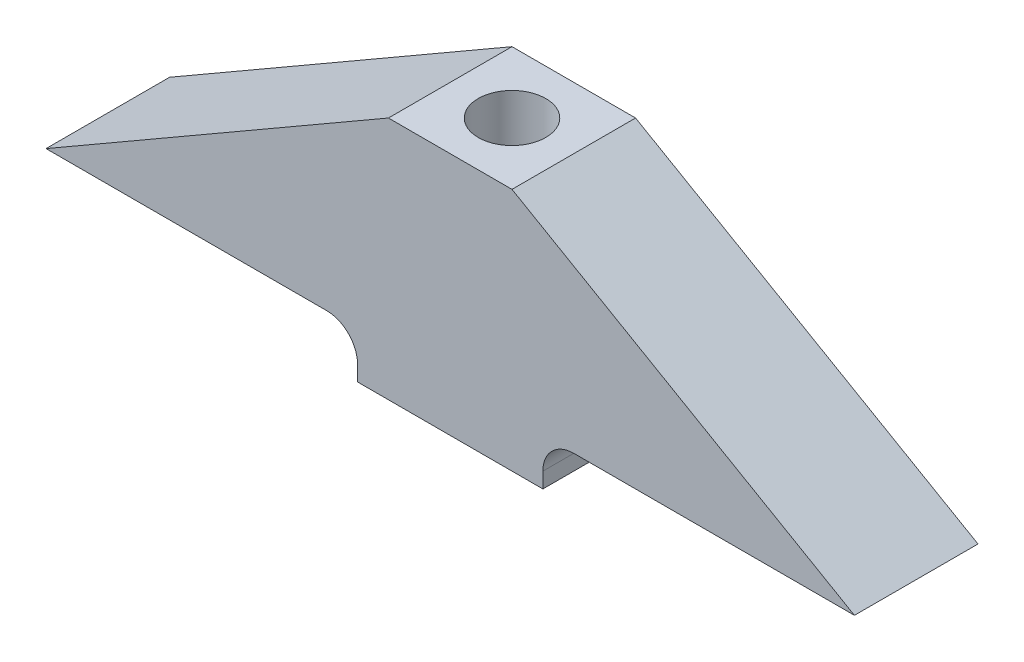
SolidWorks part; units mm, degrees
material "6061-T6 (SS)"
ref_plane "Front Plane" through (0, 0, 0) normal (0, 0, 1) x (1, 0, 0)
ref_plane "Top Plane" through (0, 0, 0) normal (0, 1, 0) x (1, 0, 0)
ref_plane "Right Plane" through (0, 0, 0) normal (1, 0, 0) x (0, 0, -1)
sketch "Sketch1" plane through (0, 0, 0) normal (0, 0, 1) x (1, 0, 0)
  line L0 (0, 0) -> (64.0405, 0)
  line L1 (166.1811, 0) -> (95.7905, 40.64)
  line L2 (95.7905, 40.64) -> (70.3905, 40.64)
  line L3 (70.3905, 40.64) -> (0, 0)
  line L4 (64.0405, 0) -> (64.0405, -9.525)
  line L5 (64.0405, -9.525) -> (102.1405, -9.525)
  line L6 (102.1405, -9.525) -> (102.1405, 0)
  line L7 (102.1405, 0) -> (166.1811, 0)
  point P8 (83.0905, -9.525)
  point P10 (83.0905, 40.64)
  dimension "D1" = 30
  dimension "D2" = 30
  dimension "D3" = 25.4
  dimension "D4" = 40.64
  dimension "D5" = 9.525
  dimension "D6" = 38.1
extrude "Boss-Extrude1" add sketch "Sketch1" along normal blind 25.4
hole_wizard "35/64 (0.54688) Diameter Hole1" positions "Sketch2" profile "Sketch3" hole size "35/64" standard "ANSI Inch"
sketch "Sketch2" plane through (0, 40.64, 0) normal (0, 1, 0) x (1, 0, 0)
  point P0 (83.0905, -12.7)
  dimension "D1" = 12.7
  dimension "D2" = 12.7
sketch "Sketch3" plane through (83.0905, 40.64, 12.7) normal (1, 0, 0) x (0, 0, 1)
  line L0 (0, 0) -> (0, 39.2252)
  line L1 (0, 39.2252) -> (6.9454, 35.052)
  line L2 (6.9454, 35.052) -> (6.9454, 0)
  line L5 (6.9454, 0) -> (0, 0)
  line L10 (0, 39.2252) -> (-6.9454, 35.052) construction
  line L11 (0, -6.35) -> (0, 107.95) construction
  dimension "Hole Dia." = 13.8908
  dimension "Hole Depth" = 35.052
  dimension "Drill Angle" = 118
hole_wizard "#10-32 Tapped Hole1" positions "Sketch4" profile "Sketch5" tap size "#10-32" standard "ANSI Inch"
sketch "Sketch4" plane through (0, -9.525, 0) normal (0, -1, 0) x (-1, 0, 0)
  point P0 (-92.6155, -15.875)
  point P3 (-73.5655, -9.525)
  dimension "D1" = 9.525
  dimension "D2" = 9.525
  dimension "D3" = 9.525
  dimension "D4" = 9.525
sketch "Sketch5" plane through (92.6155, -9.525, 15.875) normal (1, 0, 0) x (0, 0, -1)
  line L0 (0, 0) -> (0, 9.8493)
  line L1 (0, 9.8493) -> (2.0193, 8.636)
  line L2 (2.0193, 8.636) -> (2.0193, 0)
  line L5 (2.0193, 0) -> (0, 0)
  line L10 (0, 9.8493) -> (-2.0193, 8.636) construction
  line L11 (0, -6.35) -> (0, 107.95) construction
  dimension "Tap Drill Dia." = 4.0386
  dimension "Tap Drill Depth" = 8.636
  dimension "Drill Angle" = 118
cosmetic thread "Hole Thread1" parameters "D1"=6.35, "D2"=4.826
cosmetic thread "Hole Thread2" parameters "D1"=6.35, "D2"=4.826
fillet "Fillet1" radius 6.35 2 edges at (102.1405, 0, 12.7) (64.0405, 0, 12.7)
